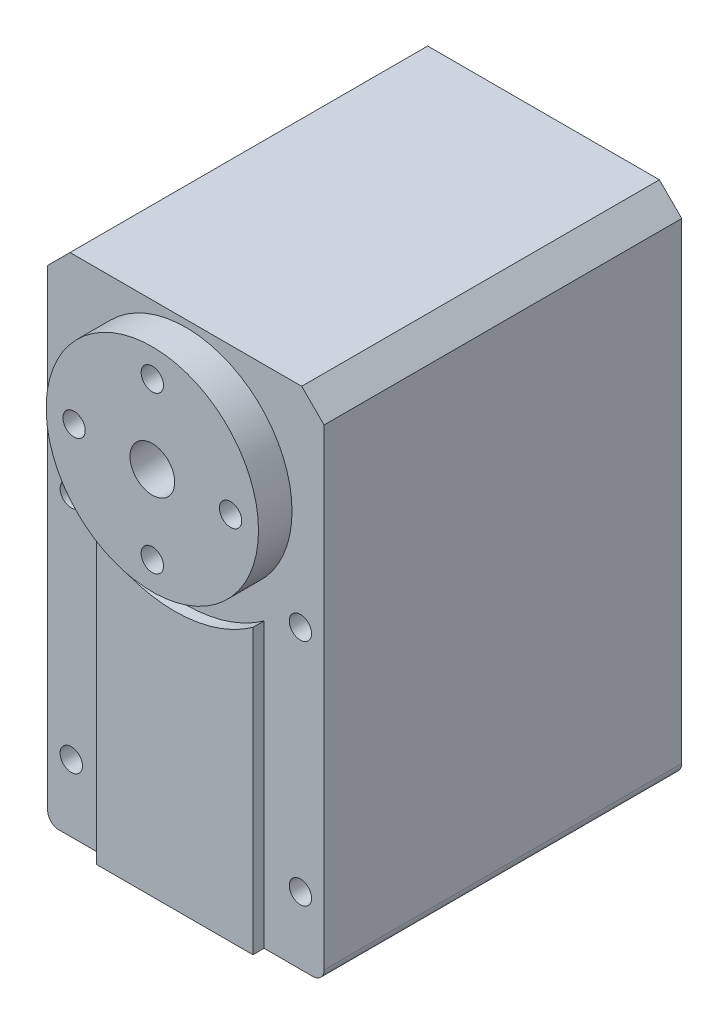
SolidWorks part; units mm, degrees
ref_plane "정면" through (0, 0, 0) normal (0, 0, 1) x (1, 0, 0)
ref_plane "윗면" through (0, 0, 0) normal (0, 1, 0) x (1, 0, 0)
ref_plane "우측면" through (0, 0, 0) normal (1, 0, 0) x (0, 0, -1)
sketch "스케치1" plane through (0, 0, 0) normal (0, 0, 1) x (1, 0, 0)
  line L1 (-12.365, 22.615) -> (12.365, 22.615)
  line L2 (-12.365, 22.615) -> (-12.365, -22.615)
  line L3 (-12.365, -22.615) -> (12.365, -22.615)
  line L4 (12.365, 22.615) -> (12.365, -22.615)
  line L5 (-12.365, 22.615) -> (12.365, -22.615) construction
  line L6 (-12.365, -22.615) -> (12.365, 22.615) construction
  point P0 (0, 0)
  dimension "D1" = 24.73
  dimension "D2" = 45.23
extrude "보스-돌출1" add sketch "스케치1" along normal blind 32
chamfer "모따기1" distance 2 angle 45 2 edges at (-12.365, 22.615, 16) (12.365, 22.615, 16)
sketch "스케치2" plane through (0, 0, 32) normal (0, 0, 1) x (1, 0, 0)
  line L0 (-12.365, -22.615) -> (12.365, -22.615) construction
  line L1 (-7, -22.615) -> (7, -22.615)
  line L2 (-7, -22.615) -> (-7, 2.7532)
  line L4 (7, -22.615) -> (7, 2.7532)
  arc A0 (-7, 2.7532) -> (7, 2.7532) centre (0, 12.5) ccw
  dimension "D4" = 24
  dimension "D1" = 14
  dimension "D2" = 7
  dimension "D3" = 12.5
extrude "보스-돌출2" add sketch "스케치2" along normal blind 1
sketch "스케치3" plane through (0, 0, 32) normal (0, 0, 1) x (1, 0, 0)
  line L0 (7, -22.615) -> (12.365, -22.615) construction
  line L1 (-10.25, -16.615) -> (10.25, -16.615) construction
  line L2 (-10.25, -16.615) -> (-10.25, 3.885) construction
  line L3 (-10.25, 3.885) -> (10.25, 3.885) construction
  line L4 (10.25, -16.615) -> (10.25, 3.885) construction
  circle A0 centre (-10.25, 3.885) radius 1
  circle A1 centre (-10.25, -16.615) radius 1
  circle A2 centre (10.25, -16.615) radius 1
  circle A3 centre (10.25, 3.885) radius 1
  dimension "D5" = 2
  dimension "D1" = 20.5
  dimension "D2" = 20.5
  dimension "D3" = 6
  dimension "D4" = 10.25
extrude "컷-돌출1" cut sketch "스케치3" against normal blind 4
sketch "스케치4" plane through (0, 0, 32) normal (0, 0, 1) x (1, 0, 0)
  circle A0 centre (0, 12.5) radius 9.5
  dimension "D1" = 12.5
  dimension "D2" = 19
extrude "보스-돌출3" add sketch "스케치4" along normal blind 3
sketch "스케치5" plane through (0, 0, 35) normal (0, 0, 1) x (1, 0, 0)
  circle A0 centre (0, 12.5) radius 7 construction
  circle A5 centre (0, 12.5) radius 2
  circle A6 centre (0, 19.5) radius 1
  circle A7 centre (7, 12.5) radius 1
  circle A8 centre (0, 12.5) radius 7 construction
  circle A9 centre (0, 5.5) radius 1
  circle A10 centre (0, 12.5) radius 7 construction
  circle A11 centre (-7, 12.5) radius 1
  circle A12 centre (0, 12.5) radius 7 construction
  point P18 (0, 12.5)
  dimension "D1" = 14
  dimension "D2" = 2
  dimension "D3" = 4
  dimension "D4" = 4
extrude "컷-돌출2" cut sketch "스케치5" against normal blind 3
sketch "스케치6" plane through (0, 0, 0) normal (0, 0, -1) x (-1, 0, 0)
  line L0 (-12.365, -22.615) -> (-12.365, 20.615) construction
  line L1 (-10.165, -18.115) -> (10.165, -18.115)
  line L2 (-10.165, -18.115) -> (-10.165, -6.115)
  line L3 (-10.165, -6.115) -> (10.165, -6.115)
  line L4 (10.165, -18.115) -> (10.165, -6.115)
  line L5 (12.365, 20.615) -> (12.365, -22.615) construction
  line L6 (12.365, -22.615) -> (-12.365, -22.615) construction
  dimension "D1" = 2.2
  dimension "D2" = 2.2
  dimension "D3" = 4.5
  dimension "D4" = 12
extrude "보스-돌출4" add sketch "스케치6" along normal blind 2
chamfer "모따기2" distance 2 angle 45 1 edges at (0, -6.115, -2)
sketch "스케치7" plane through (0, 0, 0) normal (0, 0, -1) x (-1, 0, 0)
  line L0 (12.365, 20.615) -> (12.365, -22.615) construction
  line L1 (11.165, -6.115) -> (-11.165, -6.115)
  line L2 (11.165, -6.115) -> (11.165, -1.115)
  line L3 (11.165, -1.115) -> (-11.165, -1.115)
  line L4 (-11.165, -6.115) -> (-11.165, -1.115)
  line L5 (-12.365, -22.615) -> (-12.365, 20.615) construction
  line L6 (10.165, -6.115) -> (-10.165, -6.115) construction
  dimension "D1" = 1.2
  dimension "D2" = 1.2
  dimension "D3" = 5
extrude "컷-돌출3" cut sketch "스케치7" against normal blind 2
sketch "스케치8" plane through (0, 0, 0) normal (0, 0, -1) x (-1, 0, 0)
  circle A0 centre (0, 12.5) radius 3
  dimension "D1" = 12.5
  dimension "D2" = 6
extrude "보스-돌출5" add sketch "스케치8" along normal blind 4.1
sketch "스케치9" plane through (0, 0, 0) normal (0, 0, -1) x (-1, 0, 0)
  line L0 (12.365, -22.615) -> (-12.365, -22.615) construction
  line L1 (-10.25, -20.615) -> (10.25, -20.615) construction
  line L2 (-10.25, -20.615) -> (-10.25, 3.885) construction
  line L3 (-10.25, 3.885) -> (10.25, 3.885) construction
  line L4 (10.25, -20.615) -> (10.25, 3.885) construction
  circle A0 centre (-10.25, 3.885) radius 1
  circle A1 centre (10.25, 3.885) radius 1
  circle A2 centre (-10.25, -20.615) radius 1
  circle A3 centre (10.25, -20.615) radius 1
  dimension "D5" = 2
  dimension "D1" = 20.5
  dimension "D2" = 24.5
  dimension "D3" = 10.25
  dimension "D4" = 2
extrude "컷-돌출4" cut sketch "스케치9" against normal blind 4
fillet "필렛1" radius 1 2 edges at (-12.365, -22.615, 16) (12.365, -22.615, 16)
